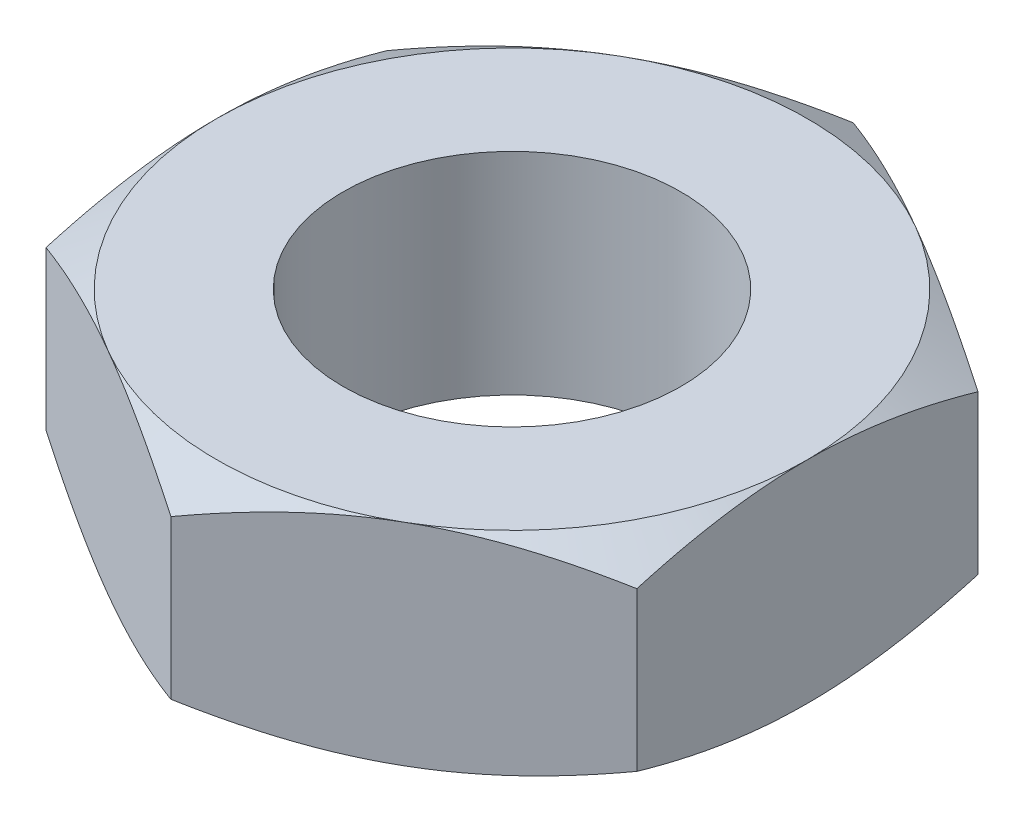
SolidWorks part; units mm, degrees
material "Alloy Steel"
ref_plane "Front Plane" through (0, 0, 0) normal (0, 0, 1) x (1, 0, 0)
ref_plane "Top Plane" through (0, 0, 0) normal (0, 1, 0) x (1, 0, 0)
ref_plane "Right Plane" through (0, 0, 0) normal (1, 0, 0) x (0, 0, -1)
sketch "Sketch1" plane through (0, 0, 0) normal (0, 1, 0) x (1, 0, 0)
  line L1 (-5.5563, 3.2079) -> (-5.5563, -3.2079)
  line L2 (-5.5563, -3.2079) -> (0, -6.4158)
  line L3 (0, -6.4158) -> (5.5562, -3.2079)
  line L4 (5.5562, -3.2079) -> (5.5562, 3.2079)
  line L5 (5.5562, 3.2079) -> (0, 6.4158)
  line L6 (0, 6.4158) -> (-5.5563, 3.2079)
  circle A0 centre (0, 0) radius 5.5563 construction
  circle A1 centre (0, 0) radius 3.175
  dimension "Thread Size" = 6.35
  dimension "Hex" = 11.1125
extrude "Boss-Extrude1" add sketch "Sketch1" along normal mid plane 3.9688
sketch "Sketch2" plane through (0, 1.9844, 0) normal (0, 1, 0) x (1, 0, 0)
  circle A0 centre (0, 0) radius 3.175 construction
  circle A1 centre (0, 0) radius 3.175
curve "Helix/Spiral1" [suppressed] pitch 0.9071 height 4.8759 turns 5.375 parameters "Pitch"=0.9071
sketch "Sketch3" plane through (0, 0, 0) normal (1, 0, 0) x (0, 0, -1)
  line L0 (2.5858, 2.4379) -> (3.175, 2.7781)
  line L1 (3.175, 2.7781) -> (3.175, 1.9844)
  line L2 (3.175, 1.9844) -> (2.5858, 2.3246)
  line L3 (2.5858, 2.3246) -> (2.5858, 2.4379)
  line L4 (2.8804, 2.608) -> (2.8804, 2.1545) construction
  line L5 (2.5858, 2.3812) -> (3.175, 2.3812) construction
  line L6 (3.175, 1.9844) -> (-3.175, 1.9844) construction
  dimension "D1" = 60
  dimension "D2" = 0.1134
  dimension "D3" = 0.4536
sweep "Sweep1" [suppressed] add profiles "Sketch3" path "Helix/Spiral1"
sketch "Sketch4" plane through (0, 1.9844, 0) normal (0, 1, 0) x (1, 0, 0)
  circle A1 centre (0, 0) radius 3.175
  circle A2 centre (0, 0) radius 3.175
  dimension "D1" = 0
extrude "Cut-Extrude1" [suppressed] cut sketch "Sketch4" along normal through all and the other way through all draft 45
sketch "Sketch5" plane through (0, 1.9844, 0) normal (0, 1, 0) x (1, 0, 0)
  circle A0 centre (0, 0) radius 5.5563 construction
  circle A1 centre (0, 0) radius 5.5563
extrude "Cut-Extrude2" cut sketch "Sketch5" against normal through all draft 60 flip side to cut
mirror "Mirror1" about plane through (0, 0, 0) normal (0, 1, 0) of "Cut-Extrude2", "Cut-Extrude1"
move or copy body "Body-Move/Copy1" [suppressed] bodies to move or copy 105 parameters "D1"=0, "D2"=0, "D3"=0
move or copy body "Body-Move/Copy2" [suppressed] bodies to move or copy 106 parameters "D1"=0, "D2"=0, "D3"=0
move or copy body "Body-Move/Copy3" [suppressed] bodies to move or copy 107 parameters "D1"=0, "D2"=0, "D3"=0
move or copy body "Body-Move/Copy4" [suppressed] bodies to move or copy 108 parameters "D1"=0, "D2"=0, "D3"=0
move or copy body "Body-Move/Copy5" [suppressed] bodies to move or copy 109 parameters "D1"=0, "D2"=0, "D3"=0
move or copy body "Body-Move/Copy6" [suppressed] bodies to move or copy 110 parameters "D1"=0, "D2"=0, "D3"=0
move or copy body "Body-Move/Copy7" [suppressed] bodies to move or copy 111 parameters "D1"=0, "D2"=0, "D3"=0
move or copy body "Body-Move/Copy8" [suppressed] bodies to move or copy 112 parameters "D1"=0, "D2"=0, "D3"=0
equation "\"D2@Sketch3\" = \"Pitch@Helix/Spiral1\"*.125"
equation "\"D3@Sketch3\" = \"Pitch@Helix/Spiral1\"*.5"
equation "\"D3@Helix/Spiral1\" = \"Height@Boss-Extrude1\"+\"Pitch@Helix/Spiral1\""
